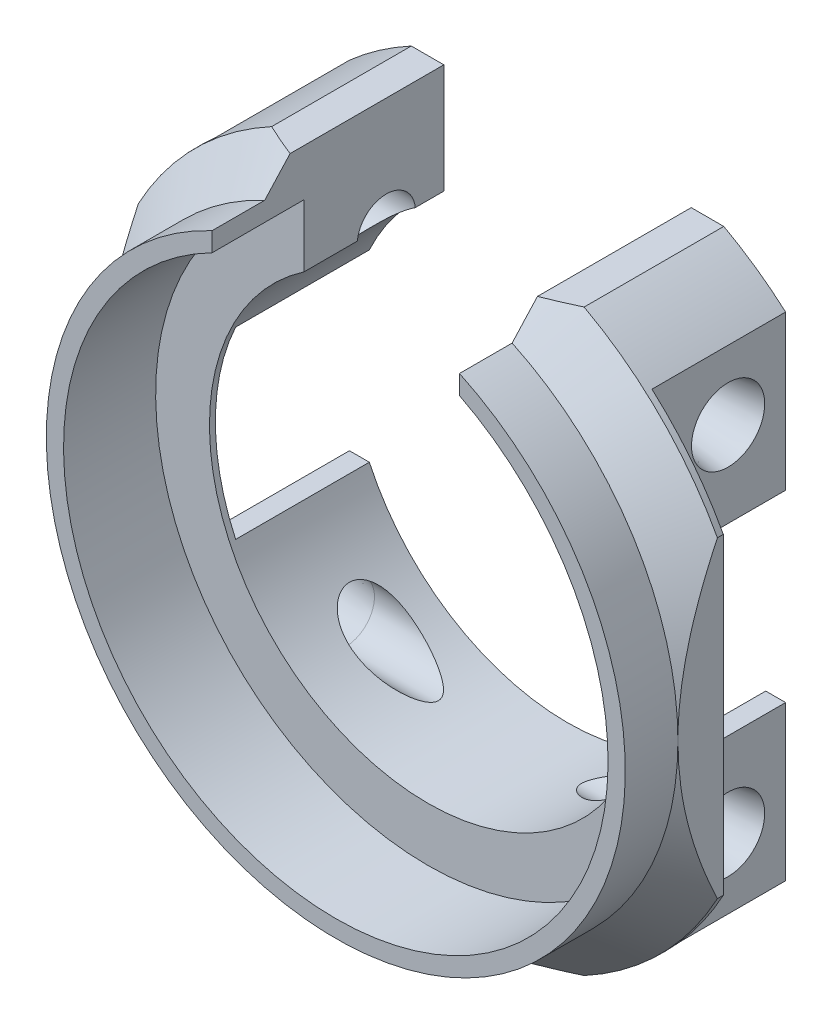
SolidWorks part; units mm, degrees
material "6061-T6 (SS)"
ref_plane "Front Plane" through (0, 0, 0) normal (0, 0, 1) x (1, 0, 0)
ref_plane "Top Plane" through (0, 0, 0) normal (0, 1, 0) x (1, 0, 0)
ref_plane "Right Plane" through (0, 0, 0) normal (1, 0, 0) x (0, 0, -1)
sketch "Sketch1" plane through (0, 0, 0) normal (0, 0, 1) x (1, 0, 0)
  line L1 (-16.637, -17.145) -> (16.637, -17.145) construction
  line L2 (-16.637, -17.145) -> (-16.637, 17.145) construction
  line L3 (-16.637, 17.145) -> (16.637, 17.145) construction
  line L4 (16.637, -17.145) -> (16.637, 17.145) construction
  line L5 (0, 17.145) -> (0, -17.145) construction
  line L6 (-16.637, 0) -> (16.637, 0) construction
  line L7 (-22, -22) -> (22, -22)
  line L8 (-22, -22) -> (-22, 22)
  line L9 (-22, 22) -> (22, 22)
  line L10 (22, -22) -> (22, 22)
  line L11 (0, 22) -> (0, -22) construction
  line L12 (-22, 0) -> (22, 0) construction
  circle A0 centre (0, 0) radius 16.002 construction
  circle A1 centre (0, 0) radius 16.602
  point P0 (0, 0)
  dimension "D3" = 32.004
  dimension "D1" = 33.274
  dimension "D2" = 34.29
  dimension "D4" = 44
  dimension "D6" = 0.6
extrude "Boss-Extrude1" add sketch "Sketch1" along normal blind 0.45
sketch "Sketch2" plane through (0, 0, 0) normal (0, 0, -1) x (-1, 0, 0)
  line L0 (-22, 22) -> (22, 22) construction
  line L1 (-16.5735, -22) -> (16.5735, -22)
  line L2 (-16.5735, -22) -> (-16.5735, 22)
  line L3 (-16.5735, 22) -> (16.5735, 22)
  line L4 (16.5735, -22) -> (16.5735, 22)
  line L5 (0, 22) -> (0, -22) construction
  line L6 (-16.5735, 0) -> (16.5735, 0) construction
  line L7 (15.0611, 6.985) -> (16.5735, 6.985)
  line L9 (15.0611, -6.985) -> (16.5735, -6.985)
  line L11 (-15.0611, -6.985) -> (-16.5735, -6.985)
  line L12 (-15.0611, 6.985) -> (-16.5735, 6.985)
  circle A0 centre (0, 0) radius 16.602 construction
  circle A1 centre (0, 0) radius 16.602
  point P0 (0, 0)
  circle M15 centre (0, 0) radius 16.602
  dimension "D1" = 33.147
  dimension "D2" = 6.985
extrude "Boss-Extrude2" add sketch "Sketch2" along normal blind 10.16 contours L7 L4 L3 M15 | L9 L1 L4 M15 region at (0, -17.0395, 0) region at (0, 17.0395, 0)
sketch "Sketch3" plane through (-16.5735, 0, 0) normal (-1, 0, 0) x (0, 0, 1)
  line L0 (0, 6.985) -> (0, 22) construction
  circle A0 centre (-5.788, 13.4747) radius 2.7813
  circle A1 centre (-5.788, -13.4747) radius 2.7813
  point P7 (0, 0)
  dimension "D3" = 5.5626
  dimension "D1" = 26.9494
  dimension "D2" = 13.4747
  dimension "D4" = 5.788
extrude "Cut-Extrude1" cut sketch "Sketch3" against normal blind 4.064 draft 8
mirror "Mirror1" about plane through (0, 0, 0) normal (1, 0, 0) of "Cut-Extrude1"
sketch "Sketch4" plane through (-12.5095, 0, 0) normal (-1, 0, 0) x (0, 0, 1)
  circle A0 centre (-5.788, -13.4747) radius 2.2101 construction
  circle A1 centre (-5.788, 13.4747) radius 2.2101 construction
  circle A2 centre (-5.788, -13.4747) radius 2.2101
  circle A3 centre (-5.788, 13.4747) radius 2.2101
extrude "Cut-Extrude2" cut sketch "Sketch4" against normal through all
sketch "Sketch5" plane through (0, 0, 0.45) normal (0, 0, 1) x (1, 0, 0)
  circle A0 centre (0, 0) radius 18.4912 construction
  dimension "D1" = 36.9824
sketch "Sketch6" plane through (0, 0, 0.45) normal (0, 0, 1) x (1, 0, 0)
  line L0 (-22, 22) -> (-22, -22) construction
  line L1 (-25, -25) -> (25, -25)
  line L2 (-25, -25) -> (-25, 25)
  line L3 (-25, 25) -> (25, 25)
  line L4 (25, -25) -> (25, 25)
  line L5 (0, 25) -> (0, -25) construction
  line L6 (-25, 0) -> (25, 0) construction
  line L8 (-22, -22) -> (22, -22) construction
  point P0 (0, 0)
  dimension "D1" = 3
  dimension "D2" = 3
chamfer "Chamfer2" distance 2 angle 45 1 edges at (0, -22, -10.16)
sketch "Sketch12" plane through (0, 0, 0.45) normal (0, 0, 1) x (1, 0, 0)
  line L0 (0, 25) -> (0, -25) construction
  circle A0 centre (0, 0) radius 20.291 construction
  circle A1 centre (0, 0) radius 22
  circle A2 centre (0, 0) radius 20.691
  dimension "D1" = 40.582
  dimension "D2" = 44
  dimension "D3" = 0.4
extrude "Boss-Extrude4" add sketch "Sketch12" along normal blind 7
sketch "Sketch13" plane through (0, 0, 0.45) normal (0, 0, 1) x (1, 0, 0)
  circle A0 centre (0, 0) radius 25
  circle A1 centre (0, 0) radius 53.181
  circle A2 centre (0, 0) radius 22 construction
  dimension "D1" = 3
extrude "Cut-Extrude9" cut sketch "Sketch13" against normal through all
chamfer "Chamfer3" distance 3 angle 45 4 edges at (15.5563, 15.5563, 0.45) (-15.5563, 15.5563, 0.45) (-15.5563, -15.5563, 0.45) (15.5563, -15.5563, 0.45)
sketch "Sketch14" plane through (0, 0, 7.45) normal (0, 0, 1) x (1, 0, 0)
  line L0 (0, 22) -> (-11.8743, 22) construction
  line L1 (-9.4, 22) -> (9.4, 22)
  line L2 (-9.4, 22) -> (-9.4, 13.6845)
  line L3 (-9.4, 13.6845) -> (9.4, 13.6845)
  line L4 (9.4, 22) -> (9.4, 13.6845)
  line L5 (0, 25) -> (0, -25) construction
  circle A0 centre (0, 0) radius 16.602 construction
  point P8 (0, 0)
  dimension "D1" = 18.8
  dimension "D2" = 9.4
extrude "Cut-Extrude10" cut sketch "Sketch14" against normal through all
